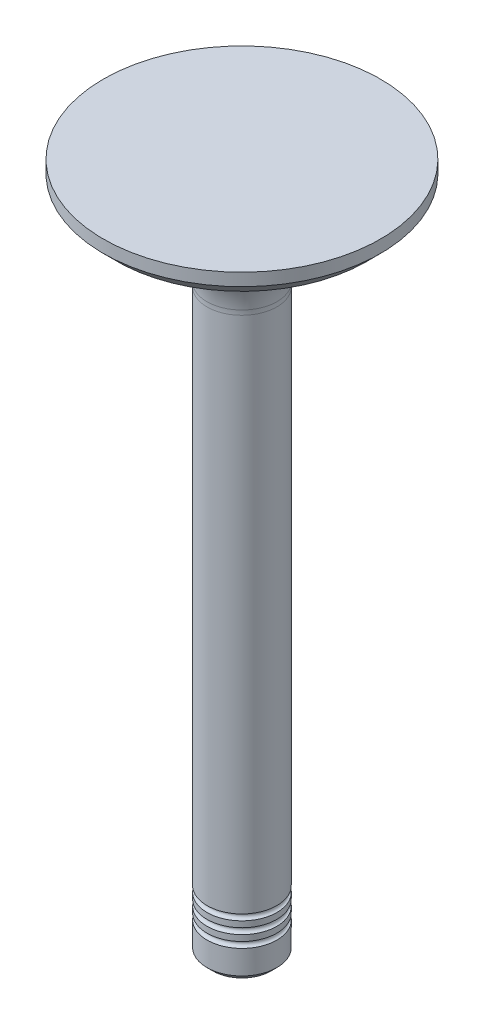
SolidWorks part; units mm, degrees
material "21-2N"
ref_plane "Front Plane" through (0, 0, 0) normal (0, 0, 1) x (1, 0, 0)
ref_plane "Top Plane" through (0, 0, 0) normal (0, 1, 0) x (1, 0, 0)
ref_plane "Right Plane" through (0, 0, 0) normal (1, 0, 0) x (0, 0, -1)
sketch "Sketch1" plane through (0, 0, 0) normal (0, 0, 1) x (1, 0, 0)
  line L0 (0, 105.7218) -> (0, -9.6782) construction
  line L1 (0, 105.7218) -> (-23.22, 105.7218)
  line L2 (-23.22, 105.7218) -> (-23.22, 103.6218)
  line L3 (-23.22, 103.6218) -> (-20.898, 101.2998)
  line L4 (0, 105.7218) -> (0, -9.6782)
  line L5 (-5.85, 87.4698) -> (-5.85, -9.6782)
  line L6 (-5.85, -9.6782) -> (0, -9.6782)
  arc A0 (-20.898, 101.2998) -> (-5.85, 87.4698) centre (-20.3114, 86.8364) cw
  point P9 (0, 0)
  dimension "D2" = 23.22
  dimension "D3" = 2.1
  dimension "D4" = 45
  dimension "D1" = 5.85
  dimension "D6" = 115.4
  dimension "D5" = 2.322
  dimension "D8" = 16.152
revolve "Revolve1" add sketch "Sketch1" angle 360 about L0
fillet "Fillet1" radius 10 1 edges at (-5.85, 87.4698, 0)
chamfer "Chamfer1" distance 1 angle 45 1 edges at (-5.85, -9.6782, 0)
sketch "Sketch2" plane through (0, 0, 0) normal (1, 0, 0) x (0, 0, -1)
  line L1 (-5.85, 87.1884) -> (-5.85, -8.6782) construction
  line L2 (-7.85, -1.6782) -> (-5.85, -1.6782)
  line L3 (-7.85, -2.6782) -> (-5.85, -2.6782)
  line L4 (0, -8.6782) -> (0, 87.9749) construction
  line L5 (5.85, -8.6782) -> (-5.85, -8.6782) construction
  line L6 (5.881, 87.9749) -> (-5.881, 87.9749) construction
  line L7 (-7.85, -2.6782) -> (-7.85, -1.6782)
  line L8 (-7.85, -4.6782) -> (-5.85, -4.6782)
  line L9 (-7.85, -4.6782) -> (-7.85, -3.6782)
  line L10 (-7.85, -3.6782) -> (-5.85, -3.6782)
  line L12 (-7.85, 0.3218) -> (-5.85, 0.3218)
  line L13 (-7.85, -0.6782) -> (-5.85, -0.6782)
  line L14 (-7.85, -0.6782) -> (-7.85, 0.3218)
  arc A1 (-5.85, -4.6782) -> (-5.85, -3.6782) centre (-5.85, -4.1782) ccw
  arc A2 (-5.85, -2.6782) -> (-5.85, -1.6782) centre (-5.85, -2.1782) ccw
  arc A3 (-5.85, -0.6782) -> (-5.85, 0.3218) centre (-5.85, -0.1782) ccw
  point P0 (-5.85, 13.2218)
  point P10 (-5.805, 17.2218)
  dimension "D1" = 4
  dimension "D2" = 1
  dimension "D3" = 3
  dimension "D5" = 2
  dimension "D6" = 1
revolve "Cut-Revolve1" cut sketch "Sketch2" angle 360 about L4
sketch "Sketch3" plane through (0, 0, 0) normal (0, 0, 1) x (1, 0, 0)
  line L0 (0, 105.7218) -> (0, -4.6075) construction
  line L1 (23.22, 105.7218) -> (-23.22, 105.7218) construction
ref_plane "Mating Plane" through (0, 103.6218, 0) normal (0, 1, 0) x (1, 0, 0)
equation "\"Valve Diameter\"= 46.44mm"
equation "\"Seat Angle Beta\"= 45deg"
equation "\"Seat Diameter\"= 41.796mm"
equation "\"Stem Diameter\"= 11.61mm"
equation "\"Seat Width\"= 2.322mm"
equation "\"Max Lift\"= 16.152mm"
equation "\"Overall Length\"= 115.4mm"
equation "\"Head Thickness\"= 2.1mm"
equation "\"D2@Sketch1\"=\"Valve Diameter\"/2"
equation "\"D3@Sketch1\"=\"Head Thickness\""
equation "\"D4@Sketch1\"=\"Seat Angle Beta\""
equation "\"D1@Sketch1\"=5.85"
equation "\"D6@Sketch1\"=\"Overall Length\""
equation "\"D5@Sketch1\"=\"Seat Width\""
equation "\"D8@Sketch1\"=\"Max Lift\""
